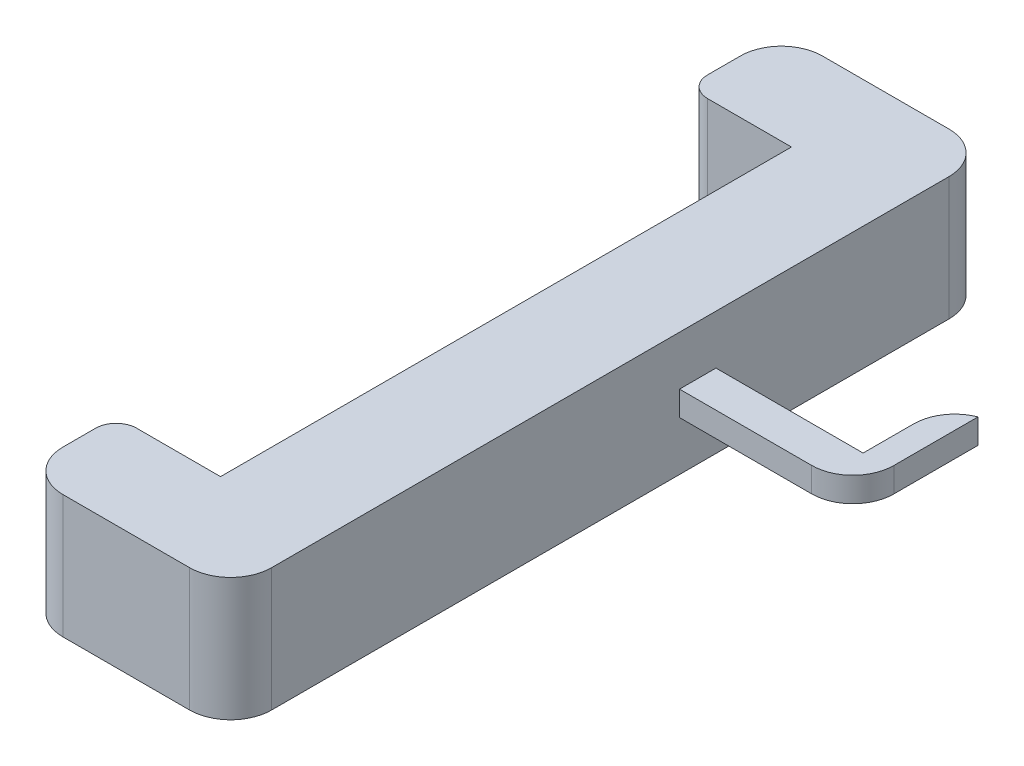
SolidWorks part; units mm, degrees
ref_plane "Front Plane" through (0, 0, 0) normal (0, 0, 1) x (1, 0, 0)
ref_plane "Top Plane" through (0, 0, 0) normal (0, 1, 0) x (1, 0, 0)
ref_plane "Right Plane" through (0, 0, 0) normal (1, 0, 0) x (0, 0, -1)
sketch "Sketch1" plane through (0, 0, 0) normal (0, 1, 0) x (1, 0, 0)
  line L0 (-55.9172, -139.6828) -> (-55.9172, 45.1258)
  line L1 (-55.9172, 45.1258) -> (-106.7172, 45.1258)
  line L2 (-55.9172, -139.6828) -> (-106.7172, -139.6828)
  line L3 (-106.7172, -139.6828) -> (-106.7172, -116.7316)
  line L4 (-106.7172, -116.7316) -> (-81.3172, -116.7316)
  line L5 (-81.3172, -116.7316) -> (-81.3172, 22.1746)
  line L6 (-81.3172, 22.1746) -> (-106.7172, 22.1746)
  line L7 (-106.7172, 22.1746) -> (-106.7172, 45.1258)
  line L8 (-55.9172, -21.5915) -> (-20.1134, -21.5915)
  line L9 (-20.1134, -21.5915) -> (-20.1134, 0)
  line L10 (-20.1134, 0) -> (-13.7527, 0)
  line L11 (-13.7527, 0) -> (-13.7527, -30.458)
  line L12 (-13.7527, -30.458) -> (-55.9172, -30.458)
  dimension "D1" = 25.4
  dimension "D2" = 138.9062
  dimension "D3" = 50.8
extrude "Boss-Extrude1" add sketch "Sketch1" along normal blind 15 and the other way blind 15 contours L7 L6 L5 L4 L3 L2 L0 L1 region at (-73.6708, 0, 47.2785)
extrude "Boss-Extrude2" add sketch "Sketch1<3>" along normal blind 3 and the other way blind 3 contours L12 L11 L10 L9 L8 L0 region at (-30.0254, 0, 21.9333)
sketch "Sketch1<3>" plane through (0, 0, 0) normal (0, 1, 0) x (1, 0, 0) same geometry as "Sketch1"
fillet "Fillet1" radius 10 6 edges at (-106.7172, 0, -45.1258) (-55.9172, 0, 139.6828) (-13.7527, 0, 30.458) (-20.1134, 0, 0) (-55.9172, 0, -45.1258) (-106.7172, 0, 139.6828)
fillet "Fillet2" radius 5 2 edges at (-106.7172, 0, 116.7316) (-106.7172, 0, -22.1746)
